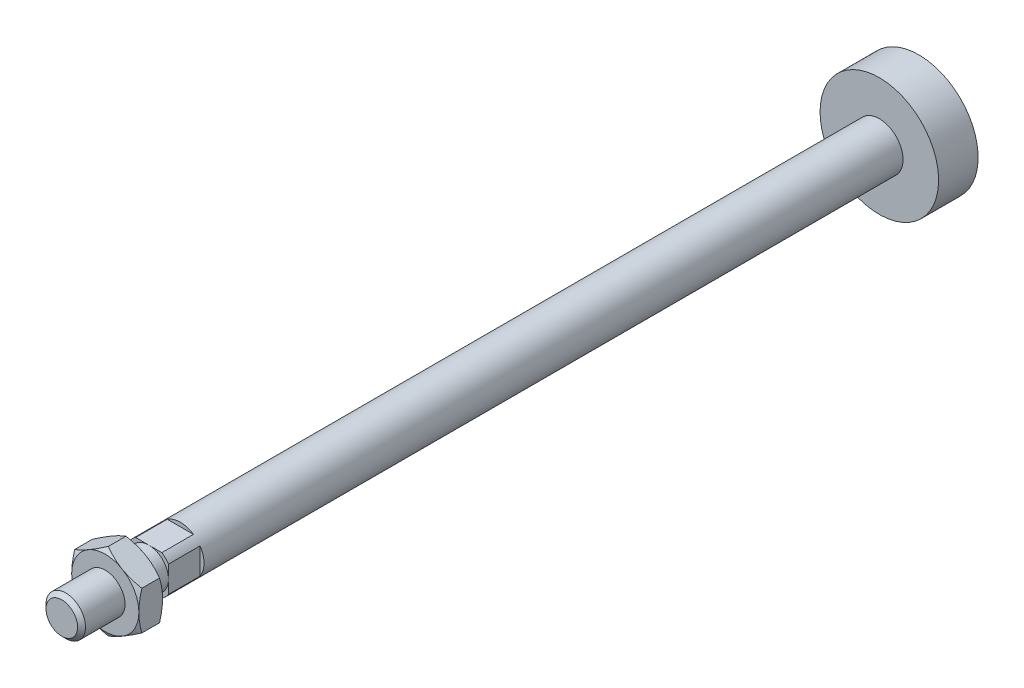
SolidWorks part; units mm, degrees
ref_plane "前视基准面" through (0, 0, 0) normal (0, 0, 1) x (1, 0, 0)
ref_plane "上视基准面" through (0, 0, 0) normal (0, 1, 0) x (1, 0, 0)
ref_plane "右视基准面" through (0, 0, 0) normal (1, 0, 0) x (0, 0, -1)
sketch "草图1" plane through (0, 0, 0) normal (0, 0, 1) x (1, 0, 0)
  line L0 (-8.5, 0) -> (8.5, 0) construction
  line L1 (0, 9.815) -> (0, -9.815) construction
  line L3 (0, 9.815) -> (-8.5, 4.9075)
  line L4 (-8.5, 4.9075) -> (-8.5, -4.9075)
  line L5 (-8.5, -4.9075) -> (0, -9.815)
  line L6 (0, -9.815) -> (8.5, -4.9075)
  line L7 (8.5, -4.9075) -> (8.5, 4.9075)
  line L8 (8.5, 4.9075) -> (0, 9.815)
  circle A0 centre (0, 0) radius 5
  circle A1 centre (0, 0) radius 6
  circle A2 centre (0, 0) radius 8.5
  point P3 (-5, 0)
  point P4 (5, 0)
  point P8 (0, 6)
  point P16 (0, 5)
  dimension "K" = 10
  dimension "V" = 12
  dimension "I" = 17
  dimension "W" = 10
sketch "草图3" plane through (0, 0, 0) normal (1, 0, 0) x (0, 0, -1)
  line L0 (0, 0) -> (216.9, 0) construction
  line L1 (0, 0) -> (0, 5)
  line L2 (0, 9.815) -> (0, 4.9075) construction
  line L3 (0, 13.2791) -> (0, -13.2791) construction
  line L4 (0, -4.9075) -> (0, -9.815) construction
  line L5 (0, 5) -> (22, 5)
  line L6 (216.9, 15) -> (216.9, 0)
  line L7 (216.9, 0) -> (0, 0)
  line L8 (22, 5) -> (22, 6)
  line L9 (22, 6) -> (206.9, 6)
  line L12 (206.9, 6) -> (206.9, 15)
  line L13 (206.9, 15) -> (216.9, 15)
  point P1 (11, 0)
  point P3 (22, 0)
  point P11 (30, 0)
  point P12 (242, 0)
  point P14 (17, 0)
  point P18 (100, 0)
  point P22 (48, 0)
  point P23 (94, 0)
  dimension "D1" = 11
  dimension "H" = 22
  dimension "E" = 30
  dimension "J" = 6
  dimension "D2" = 242
  dimension "行程" = 100
  dimension "B" = 48
  dimension "C" = 94
  dimension "缸径1" = 15
  dimension "D4" = 10
  dimension "G" = 25.1
sketch "草图4" plane through (0, 0, 0) normal (1, 0, 0) x (0, 0, -1)
  line L1 (206.9, 6) -> (206.9, 15) construction
  line L2 (206.9, 15) -> (216.9, 15) construction
  line L3 (216.9, 15) -> (216.9, 0) construction
  line L4 (216.9, 0) -> (0, 0) construction
  line L5 (0, 0) -> (0, 5) construction
  line L6 (0, 5) -> (22, 5) construction
  line L7 (22, 5) -> (22, 6) construction
  line L8 (22, 6) -> (206.9, 6) construction
  line L11 (206.9, 6) -> (206.9, 15)
  line L12 (206.9, 15) -> (216.9, 15)
  line L13 (216.9, 15) -> (216.9, 0)
  line L14 (216.9, 0) -> (0, 0)
  line L15 (0, 0) -> (0, 5)
  line L16 (0, 5) -> (22, 5)
  line L17 (22, 5) -> (22, 6)
  line L18 (22, 6) -> (206.9, 6)
revolve "旋转1" add sketch "草图4" angle 360 about L14
cosmetic thread "装饰螺纹线1" parameters "D2"=8.5
cosmetic thread "装饰螺纹线2" parameters "D2"=8.5
ref_plane "基准面1" through (0, 0, -11) normal (0, 0, 1) x (1, 0, 0)
sketch "草图5" plane through (0, 0, -11) normal (0, 0, 1) x (1, 0, 0)
  line L0 (0, 9.815) -> (-8.5, 4.9075) construction
  line L1 (-8.5, 4.9075) -> (-8.5, -4.9075) construction
  line L2 (-8.5, -4.9075) -> (0, -9.815) construction
  line L3 (0, -9.815) -> (8.5, -4.9075) construction
  line L4 (8.5, -4.9075) -> (8.5, 4.9075) construction
  line L5 (8.5, 4.9075) -> (0, 9.815) construction
  line L6 (0, 9.815) -> (-8.5, 4.9075)
  line L7 (-8.5, 4.9075) -> (-8.5, -4.9075)
  line L8 (-8.5, -4.9075) -> (0, -9.815)
  line L9 (0, -9.815) -> (8.5, -4.9075)
  line L10 (8.5, -4.9075) -> (8.5, 4.9075)
  line L11 (8.5, 4.9075) -> (0, 9.815)
  circle A0 centre (0, 0) radius 8.5 construction
  circle A1 centre (0, 0) radius 8.5
extrude "凸台-拉伸1" add sketch "草图5" against normal up to vertex (6 mm away) separate body contours L11 L6 L7 L8 L9 L10 up to point (0, 0, -17)
extrude "切除-拉伸1" cut sketch "草图5<3>" against normal blind 8 draft 60 flip side to cut contours A1
sketch "草图5<3>" plane through (0, 0, -11) normal (0, 0, 1) x (1, 0, 0) same geometry as "草图5"
extrude "切除-拉伸2" cut sketch "草图5<4>" along normal blind 8 draft 60 from vertex flip side to cut contours A1 starting at point (0, 9.8149, -17)
sketch "草图5<4>" plane through (0, 0, -11) normal (0, 0, 1) x (1, 0, 0) same geometry as "草图5"
sketch "草图6" plane through (0, 0, -22) normal (0, 0, 1) x (1, 0, 0)
  line L0 (-5, 3.3166) -> (-5, -3.3166)
  line L1 (0, 6) -> (0, -6) construction
  line L2 (5, 3.3166) -> (5, -3.3166)
  line L3 (0, 0) -> (4.2426, 4.2426) construction
  line L4 (3.3166, 5) -> (-3.3166, 5)
  line L5 (-6, 0) -> (6, 0) construction
  line L6 (3.3166, -5) -> (-3.3166, -5)
  circle A0 centre (0, 0) radius 6 construction
  circle A1 centre (0, 0) radius 6
  circle M2 centre (0, 0) radius 6
  dimension "D1" = 45
extrude "切除-拉伸3" cut sketch "草图6" against normal blind 8 contours L4 M2 | L2 M2 | L6 M2 | L0 M2 region at (-5.403, 0, -22) region at (0, 5.403, -22) region at (0, -5.403, -22) region at (5.403, 0, -22)
chamfer "倒角1" distance 1 angle 45 1 edges at (-5, 0, 0)
combine bodies "组合1" operation type add bodies to combine 104 105
